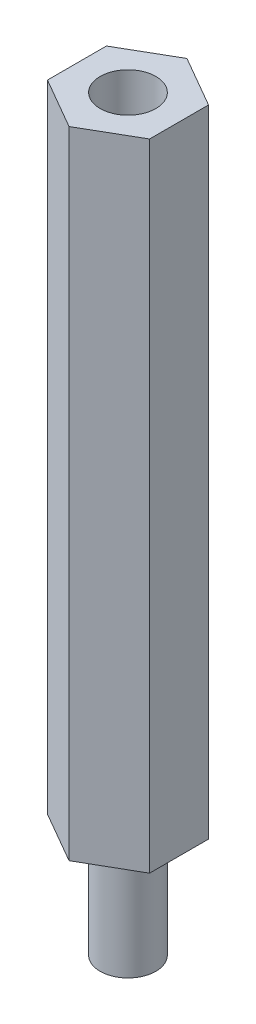
SolidWorks part; units mm, degrees
ref_plane "Front Plane" through (0, 0, 0) normal (0, 0, 1) x (1, 0, 0)
ref_plane "Top Plane" through (0, 0, 0) normal (0, 1, 0) x (1, 0, 0)
ref_plane "Right Plane" through (0, 0, 0) normal (1, 0, 0) x (0, 0, -1)
sketch "Sketch1" plane through (0, 0, 0) normal (0, 1, 0) x (1, 0, 0)
  line L1 (2.794, -1.6131) -> (2.794, 1.6131)
  line L2 (2.794, 1.6131) -> (0, 3.2262)
  line L3 (0, 3.2262) -> (-2.794, 1.6131)
  line L4 (-2.794, 1.6131) -> (-2.794, -1.6131)
  line L5 (-2.794, -1.6131) -> (0, -3.2262)
  line L6 (0, -3.2262) -> (2.794, -1.6131)
  circle A0 centre (0, 0) radius 2.794 construction
  circle A1 centre (0, 0) radius 1.524
  dimension "D2" = 3.048
  dimension "D1" = 5.588
extrude "Boss-Extrude1" add sketch "Sketch1" along normal blind 34.798 contours A1 | L5 L6 L1 L2 L3 L4 A1 region at (1.3543, 0, 2.3458) region at (0, 0, 0)
extrude "Boss-Extrude2" add sketch "Sketch1<3>" against normal blind 6.096 contours A1 region at (0, 0, 0)
sketch "Sketch1<3>" plane through (0, 0, 0) normal (0, 1, 0) x (1, 0, 0) same geometry as "Sketch1"
extrude "Cut-Extrude1" cut sketch "Sketch1<4>" against normal blind 6.096 from surface contours A1 region at (0, 0, 0) starting at face at (0, 34.798, 0)
sketch "Sketch1<4>" plane through (0, 0, 0) normal (0, 1, 0) x (1, 0, 0) same geometry as "Sketch1"
